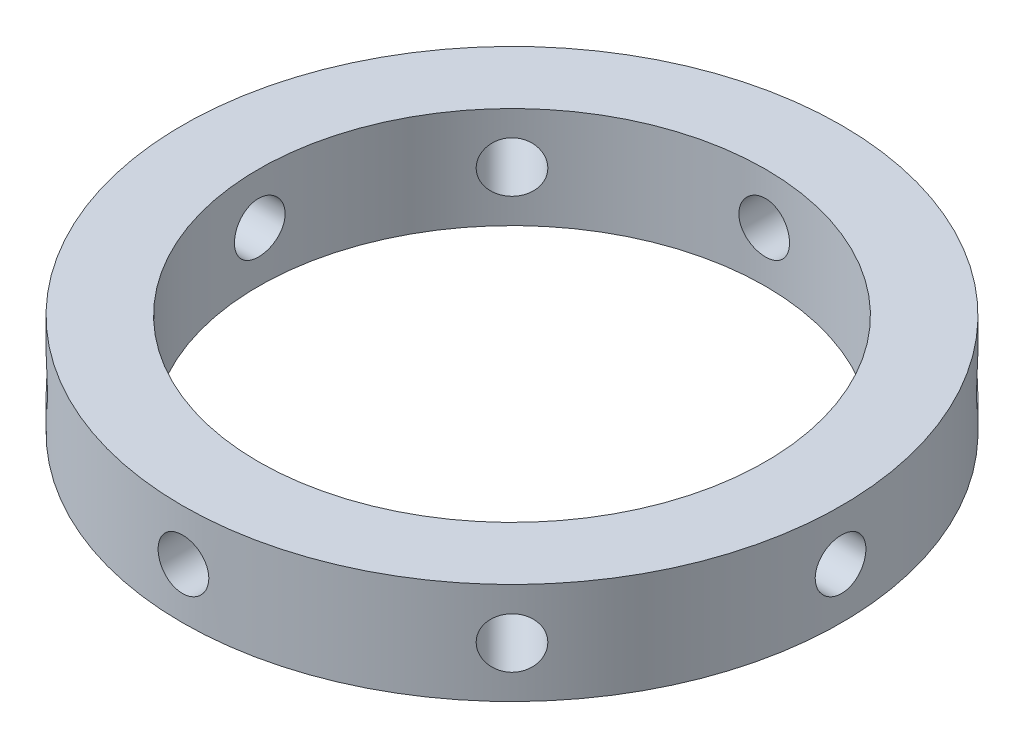
SolidWorks part; units mm, degrees
material "6061-T6 (SS)"
ref_plane "Front Plane" through (0, 0, 0) normal (0, 0, 1) x (1, 0, 0)
ref_plane "Top Plane" through (0, 0, 0) normal (0, 1, 0) x (1, 0, 0)
ref_plane "Right Plane" through (0, 0, 0) normal (1, 0, 0) x (0, 0, -1)
sketch "Sketch1" plane through (0, 0, 0) normal (0, 1, 0) x (1, 0, 0)
  circle A0 centre (0, 0) radius 31.75
  circle A1 centre (0, 0) radius 41.275
  dimension "D1" = 63.5
  dimension "D2" = 82.55
extrude "Boss-Extrude1" add sketch "Sketch1" along normal blind 12.7
ref_axis "Axis1" through (0, -0.3175, 0) along (0, 1, 0)
ref_plane "Plane1" through (0, 6.35, 0) normal (0, 1, 0) x (1, 0, 0)
ref_axis "Axis2" through (0, 6.35, -88.99) along (0, 0, 1)
hole_wizard "1/4 (0.25) Diameter Hole1" positions "3DSketch2" profile "Sketch3" hole size "1/4" standard "ANSI Inch"
sketch3d "3DSketch2"
  line L0 (0, 6.35, -88.99) -> (0, 6.35, 88.99) construction
  point P0 (0, 6.35, 41.275)
  point P3 (0, 0, 0)
sketch "Sketch3" plane through (0, 6.35, 41.275) normal (1, 0, 0) x (0, -1, 0)
  line L0 (0, 0) -> (0, 13.5917)
  line L1 (0, 13.5917) -> (3.175, 11.684)
  line L2 (3.175, 11.684) -> (3.175, 0)
  line L5 (3.175, 0) -> (0, 0)
  line L10 (0, 13.5917) -> (-3.175, 11.684) construction
  line L11 (0, -6.35) -> (0, 107.95) construction
  dimension "Hole Dia." = 6.35
  dimension "Hole Depth" = 11.684
  dimension "Drill Angle" = 118
pattern_circular "CirPattern1" count 8 over 360 about axis through (0, -0.3175, 0) along (0, 1, 0) of "1/4 (0.25) Diameter Hole1"
